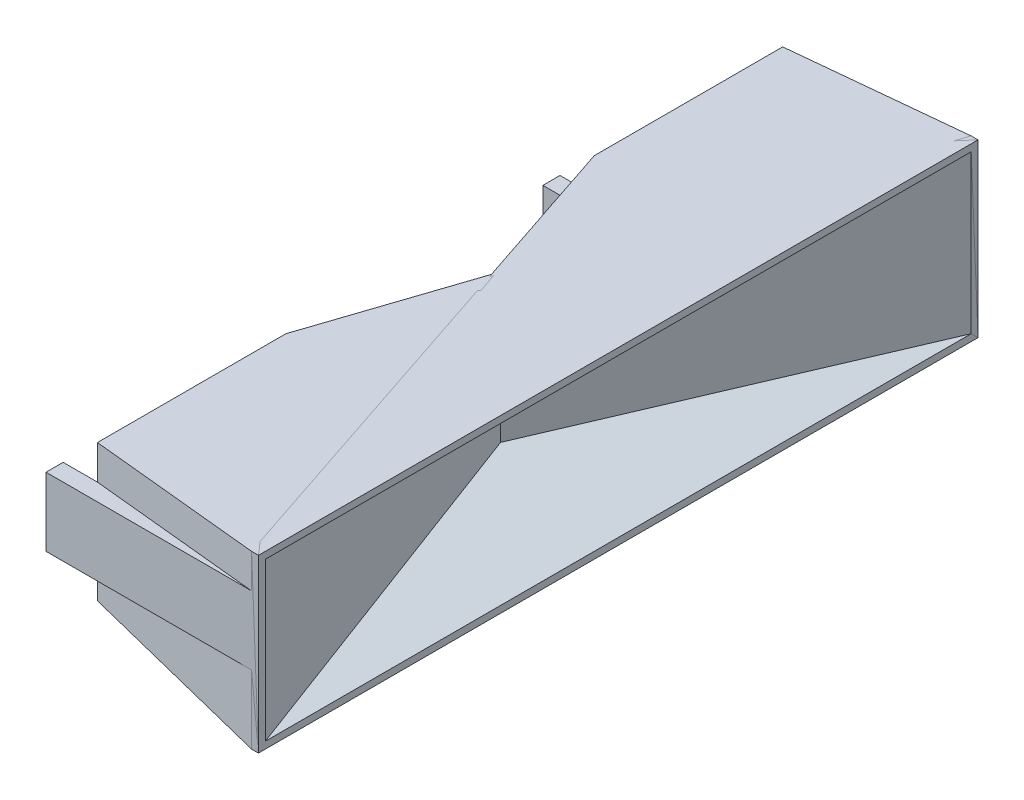
SolidWorks part; units mm, degrees
ref_plane "Front Plane" through (0, 0, 0) normal (0, 0, 1) x (1, 0, 0)
ref_plane "Top Plane" through (0, 0, 0) normal (0, 1, 0) x (1, 0, 0)
ref_plane "Right Plane" through (0, 0, 0) normal (1, 0, 0) x (0, 0, -1)
sketch "Sketch1" plane through (0, 0, 0) normal (1, 0, 0) x (0, 0, -1)
  line L0 (-103, 23) -> (103, 23)
  line L1 (-105, -25) -> (105, -25)
  line L2 (-105, -25) -> (-105, 25)
  line L3 (-105, 25) -> (105, 25)
  line L4 (105, -25) -> (105, 25)
  line L5 (-105, -25) -> (105, 25) construction
  line L6 (-105, 25) -> (105, -25) construction
  line L7 (103, -23) -> (103, 23)
  line L8 (-103, -23) -> (103, -23)
  line L9 (-103, -23) -> (-103, 23)
  point P0 (0, 0)
  dimension "D1" = 50
  dimension "D2" = 210
  dimension "D3" = 2
extrude "Boss-Extrude3" add sketch "Sketch1" along normal blind 52
sketch "Sketch3" plane through (0, 0, 0) normal (-1, 0, 0) x (0, 0, 1)
  line L4 (-105, 25) -> (-105, -25)
  line L5 (-105, -25) -> (105, -25)
  line L6 (105, -25) -> (105, 25)
  line L7 (105, 25) -> (-105, 25)
  line L8 (-105, 25) -> (-105, -25)
  line L9 (-105, -25) -> (105, -25)
  line L10 (105, -25) -> (105, 25)
  line L11 (105, 25) -> (-105, 25)
  dimension "D1" = 0
extrude "Boss-Extrude4" add sketch "Sketch3" against normal blind 2
chamfer "Chamfer1" distance 5 distance2 50 1 edges at (2, 0, 103) first distance on face at (2, 0, 0)
chamfer "Chamfer2" distance 10 distance2 50 1 edges at (2, -23, -2.5) first distance on face at (2, 0, -2.5)
chamfer "Chamfer3" distance 150 distance2 50 1 edges at (2, 5, -103) first distance on face at (2, 5, -2.5)
chamfer "Chamfer4" distance 150 distance2 50 1 edges at (0, 0, -105) first distance on face at (0, 0, 0)
chamfer "Chamfer5" distance 10 distance2 50 1 edges at (0, -25, 75) first distance on face at (0, 0, 75)
chamfer "Chamfer6" distance 5 distance2 50 1 edges at (0, 5, 105) first distance on face at (0, 5, 75)
sketch "Sketch4" plane through (0, 0, 0) normal (-1, 0, 0) x (0, 0, 1)
  line L0 (98, 23) -> (47, 23)
  line L1 (47, 23) -> (47, -13)
  line L2 (47, -13) -> (98, -13)
  line L3 (98, -13) -> (98, 23)
  line L4 (45, -15) -> (100, -15)
  line L5 (100, -15) -> (100, 25)
  line L6 (100, 25) -> (45, 25)
  line L7 (45, 25) -> (45, -15)
  line L8 (45, -15) -> (100, -15)
  line L9 (100, -15) -> (100, 25)
  line L10 (100, 25) -> (45, 25)
  line L11 (45, 25) -> (45, -15)
  dimension "D1" = 0
  dimension "D2" = 2
extrude "Cut-Extrude2" cut sketch "Sketch4" against normal blind 2 contours L0 L1 L2 L3
sketch "Sketch5" plane through (0, 0, 0) normal (-1, 0, 0) x (0, 0, 1)
  line L0 (100, -15) -> (100, 25) construction
  line L1 (100, -5) -> (105, -5)
  line L2 (100, -5) -> (100, 15)
  line L3 (100, 15) -> (105, 15)
  line L4 (105, -5) -> (105, 15)
  line L5 (45, 25) -> (45, -15) construction
  line L6 (45, -5) -> (40, -5)
  line L7 (45, -5) -> (45, 15)
  line L8 (45, 15) -> (40, 15)
  line L9 (40, -5) -> (40, 15)
  line L10 (98, -13) -> (98, 23) construction
  point P14 (98, 5)
  point P15 (100, 5)
  dimension "D1" = 5
  dimension "D2" = 5
  dimension "D3" = 20
extrude "Boss-Extrude5" add sketch "Sketch5" along normal blind 10 separate body
sketch "Sketch6" plane through (0, 0, 0) normal (1, 0, 0) x (0, 0, -1)
  line L4 (-45, 15) -> (-45, -5)
  line L5 (-45, -5) -> (-40, -5)
  line L6 (-40, -5) -> (-40, 15)
  line L7 (-40, 15) -> (-45, 15)
  line L8 (-45, 15) -> (-45, -5)
  line L9 (-45, -5) -> (-40, -5)
  line L10 (-40, -5) -> (-40, 15)
  line L11 (-40, 15) -> (-45, 15)
  line L12 (-100, -5) -> (-100, 15)
  line L13 (-100, 15) -> (-105, 15)
  line L14 (-105, 15) -> (-105, -5)
  line L15 (-105, -5) -> (-100, -5)
  line L16 (-100, -5) -> (-100, 15)
  line L17 (-100, 15) -> (-105, 15)
  line L18 (-105, 15) -> (-105, -5)
  line L19 (-105, -5) -> (-100, -5)
  dimension "D1" = 0
  dimension "D2" = 0
extrude "Boss-Extrude6" add sketch "Sketch6" along normal blind 52
sketch "Sketch7" plane through (0, -13, 0) normal (0, 1, 0) x (1, 0, 0)
  line L4 (52, -103) -> (52, 103)
  line L5 (52, 103) -> (2, -47)
  line L6 (2, -47) -> (2, -98)
  line L7 (2, -98) -> (52, -103)
  line L8 (52, -103) -> (52, 103)
  line L9 (52, 103) -> (2, -47)
  line L10 (2, -47) -> (2, -98)
  line L11 (2, -98) -> (52, -103)
  dimension "D1" = 0
extrude "Cut-Extrude3" cut sketch "Sketch7" along normal up to surface (36 mm away) up to face at (18, 23, 48.3333)
mirror "Mirror1" about plane through (0, 0, 0) normal (0, 0, 1) of bodies 111
